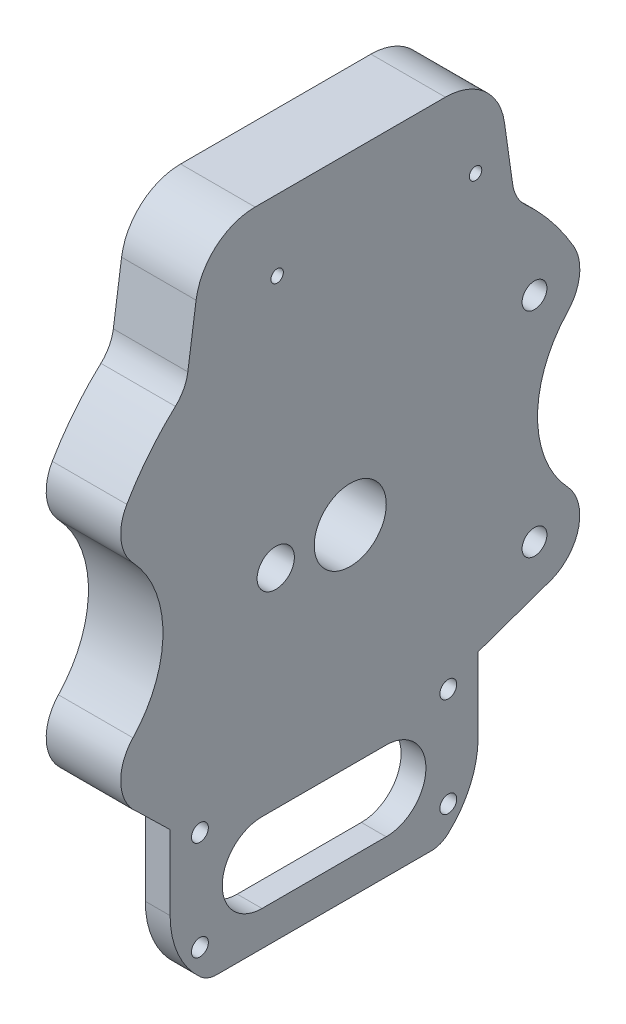
SolidWorks part; units mm, degrees
ref_plane "Płaszczyzna przednia" through (0, 0, 0) normal (0, 0, 1) x (1, 0, 0)
ref_plane "Płaszczyzna górna" through (0, 0, 0) normal (0, 1, 0) x (1, 0, 0)
ref_plane "Płaszczyzna prawa" through (0, 0, 0) normal (1, 0, 0) x (0, 0, -1)
sketch "Szkic1" plane through (0, 0, 0) normal (1, 0, 0) x (0, 0, -1)
  line L5 (0, 0) -> (0, 195.8303) construction
  line L42 (14.4695, -100) -> (-35.5305, -100) construction
  line L44 (14.4695, -84) -> (-35.5305, -84)
  line L45 (14.4695, -116) -> (-35.5305, -116)
  line L46 (30.5104, 100) -> (-9.4896, 100) construction
  line L47 (30.5104, 105) -> (-9.4896, 105) construction
  line L48 (30.5104, 95) -> (-9.4896, 95) construction
  line L49 (-10.5305, -100) -> (-10.5305, -46.7527) construction
  line L50 (-13.6636, -130) -> (20.5826, 195.8303) construction
  line L51 (0, 0) -> (120, 0) construction
  line L52 (0, 0) -> (0, -130.3815) construction
  line L53 (-72.5305, -70) -> (-85.8486, -57.0401)
  line L54 (-72.5305, -100) -> (-72.5305, -70)
  line L55 (51.4695, -70) -> (81.2407, -59.5241)
  line L56 (-35.5305, -130) -> (-53.6689, -130)
  line L57 (51.4695, -100) -> (51.4695, -70)
  line L58 (14.4695, -130) -> (32.6078, -130)
  line L59 (14.4695, -130) -> (-35.5305, -130)
  line L60 (62.0766, 109.386) -> (65.4007, 86.06)
  line L61 (-38.3166, 130) -> (38.3166, 130)
  line L62 (-62.0766, 109.386) -> (-65.4007, 86.06)
  circle A0 centre (0, 0) radius 14.5
  circle A3 centre (0, 0) radius 85.75 construction
  arc A56 (14.4695, -84) -> (14.4695, -116) centre (14.4695, -100) cw
  arc A57 (-35.5305, -116) -> (-35.5305, -84) centre (-35.5305, -100) cw
  arc A60 (30.5104, 105) -> (30.5104, 95) centre (30.5104, 100) cw construction
  arc A61 (-9.4896, 95) -> (-9.4896, 105) centre (-9.4896, 100) cw construction
  arc A62 (32.6078, -130) -> (39.3257, -127.4074) centre (32.6078, -120) ccw
  arc A63 (-60.3868, -127.4074) -> (-53.6689, -130) centre (-53.6689, -120) ccw
  arc A65 (51.4695, -100) -> (39.3257, -127.4074) centre (14.4695, -100) cw
  arc A66 (-60.3868, -127.4074) -> (-72.5305, -100) centre (-35.5305, -100) cw
  arc A67 (87.4958, -30.51) -> (81.2407, -59.5241) centre (74.4106, -42.8703) cw
  arc A68 (87.4958, -30.51) -> (87.4958, 30.51) centre (120, 0) cw
  arc A69 (89.9789, 52.1516) -> (87.4958, 30.51) centre (74.1894, 43) cw
  arc A70 (70.4086, 76.5417) -> (89.9789, 52.1516) centre (0, 0) cw
  arc A71 (65.4007, 86.06) -> (70.4086, 76.5417) centre (81.2407, 88.3174) ccw
  arc A72 (38.3166, 130) -> (62.0766, 109.386) centre (38.3166, 106) cw
  arc A73 (-38.3166, 130) -> (-62.0766, 109.386) centre (-38.3166, 106) ccw
  arc A74 (-65.4007, 86.06) -> (-70.4086, 76.5417) centre (-81.2407, 88.3174) cw
  arc A75 (-70.4086, 76.5417) -> (-89.9789, 52.1516) centre (0, 0) ccw
  arc A76 (-89.9789, 52.1516) -> (-87.4958, 30.51) centre (-74.1894, 43) ccw
  arc A77 (-87.4958, -30.51) -> (-87.4958, 30.51) centre (-120, 0) ccw
  arc A78 (-87.4958, -30.51) -> (-85.8486, -57.0401) centre (-74.1894, -43) ccw
  circle A79 centre (74.1894, -43) radius 5
  circle A80 centre (74.1894, 43) radius 5
  point P7 (-10.5305, -100)
  point P24 (-25, -70)
  point P25 (25, -70)
  point P30 (25, -100)
  point P31 (25, -130)
  point P33 (-25, -130)
  point P34 (-25, -100)
  point P41 (-25, -70)
  point P42 (25, -70)
  point P43 (-25.5104, 81)
  point P44 (25, -100)
  point P46 (-25, -130)
  point P47 (-25, -100)
  point P49 (62, -82.8995)
  point P58 (62, -100)
  point P59 (25, -100)
  point P60 (25, -137)
  point P61 (-25, -137)
  point P62 (-25, -100)
  point P63 (-62, -100)
  point P64 (-62, -82.8995)
  point P69 (10.5104, 100)
  point P72 (0, 126)
  point P192 (46.6564, -130)
  point P193 (-46.6564, -130)
  point P194 (74.1894, 43)
  point P195 (74.1894, -43)
  dimension "D1" = 29
  dimension "D7" = 171.5
extrude "Dodanie-wyciągnięcie1" add sketch "Szkic1" along normal mid plane 30
hole_wizard "Otwór gwintowany M61" positions "Sketch1" profile "Sketch2" tap size "M6" standard "ISO" end condition through all
sketch "Sketch1" plane through (-15, 0, 0) normal (1, 0, 0) x (0, 0, -1)
  line L0 (-81.5745, 104.2751) -> (63.3416, 96.6804) construction
  line L11 (0, 0) -> (0, 118.3984) construction
  line L12 (10.8009, 104.9924) -> (10.2776, 95.0061) construction
  point P50 (50.4556, 97.3557)
  point P51 (-29.4348, 101.5426)
  dimension "D1" = 93
  dimension "D2" = 40
  dimension "D3" = 40
sketch "Sketch2" plane through (-15, 101.5426, 29.4348) normal (0, 1, 0) x (0, 0, 1)
  line L0 (0, 0) -> (0, 30)
  line L1 (0, 30) -> (2.5, 30)
  line L2 (2.5, 30) -> (2.5, 0)
  line L5 (2.5, 0) -> (0, 0)
  line L11 (0, -6.35) -> (0, 107.95) construction
  dimension "Thru Tap Drill Dia." = 5
  dimension "Thru Tap Drill Depth" = 30
cosmetic thread "Gwint otworu5" parameters "D2"=6
cosmetic thread "Gwint otworu6" parameters "D2"=6
sketch "Szkic12" plane through (-15, 0, 0) normal (1, 0, 0) x (0, 0, -1)
  line L0 (0, 0) -> (0, 198.2502) construction
  line L1 (50.4556, 97.3557) -> (-29.4348, 101.5426) construction
  line L2 (28.8022, 93.4837) -> (-9.7329, 95.5032)
  line L3 (-9.2095, 105.4895) -> (29.3255, 103.47)
  arc A0 (-9.7329, 95.5032) -> (-9.2095, 105.4895) centre (-9.4712, 100.4964) cw
  arc A1 (29.3255, 103.47) -> (28.8022, 93.4837) centre (29.0639, 98.4768) cw
  circle A2 centre (-29.4348, 101.5426) radius 2.5 construction
  circle A3 centre (50.4556, 97.3557) radius 2.5 construction
  circle A4 centre (-29.4348, 101.5426) radius 2.5
  circle A5 centre (50.4556, 97.3557) radius 2.5
  point P0 (-30.2019, 101.5426)
  point P11 (0, 0)
  point P12 (0, 0)
  dimension "D3" = 5
  dimension "D1" = 93
  dimension "D2" = 10
extrude "Wytnij-wyciągnięcie2" cut sketch "Szkic12" along normal blind 10 contours A0 L3 A1 L2
sketch "Szkic16" plane through (-15, 0, 0) normal (1, 0, 0) x (0, 0, -1)
  line L5 (-35.5305, -116) -> (14.4695, -116)
  line L6 (14.4695, -84) -> (-35.5305, -84)
  line L8 (-53.6689, -130) -> (32.6078, -130)
  line L10 (-83.0611, -100) -> (40.9389, -100) construction
  line L11 (-72.5305, -70) -> (51.4695, -70)
  line L13 (-72.5305, -70) -> (-72.5305, -100)
  line L16 (51.4695, -70) -> (51.4695, -100)
  arc A6 (-35.5305, -84) -> (-35.5305, -116) centre (-35.5305, -100) ccw
  arc A7 (14.4695, -116) -> (14.4695, -84) centre (14.4695, -100) ccw
  arc A9 (32.6078, -130) -> (39.3257, -127.4074) centre (32.6078, -120) ccw
  arc A10 (-60.3868, -127.4074) -> (-53.6689, -130) centre (-53.6689, -120) ccw
  arc A20 (39.3257, -127.4074) -> (51.4695, -100) centre (14.4695, -100) ccw
  arc A21 (-72.5305, -100) -> (-60.3868, -127.4074) centre (-35.5305, -100) ccw
extrude "Wytnij-wyciągnięcie4" cut sketch "Szkic16" along normal blind 20
chamfer "Sfazowanie4" distance 10 angle 45 1 edges at (-15, -70, 10.5305)
sketch "Szkic17" plane through (-15, 0, 0) normal (1, 0, 0) x (0, 0, -1)
  line L2 (0, 0) -> (0, 36.4505) construction
  line L3 (-45.2929, 8.9572) -> (-31.5786, 10.9367)
  line L6 (-31.5786, -10.9367) -> (-45.2929, -8.9572)
  arc A7 (-45.2929, -8.9572) -> (-45.2929, 8.9572) centre (-44, 0) cw
  circle A8 centre (-30, 0) radius 7.5
  arc A10 (-18.9801, -0.8154) -> (-31.5786, -10.9367) centre (-30, 0) cw
  arc A12 (-31.5786, 10.9367) -> (-18.9801, -0.8154) centre (-30, 0) cw
  point P0 (8.9572, 38.7071)
  point P1 (-0.6678, 49.0253)
  point P2 (30, 0)
  point P3 (-8.9572, 38.7071)
  point P5 (-6.9777, 24.9929)
  point P6 (0, 26)
  point P7 (4.5988, 31.3435)
  point P8 (0, 26)
  point P9 (6.9777, 24.9929)
  point P20 (45.2929, -8.9572)
  point P21 (0, 26)
  point P22 (5.9035, 32.8594)
  point P23 (44, 0)
  point P24 (45.2929, 8.9572)
extrude "Wytnij-wyciągnięcie5" cut sketch "Szkic17" along normal blind 5 contours A8 | A7 L3 A12 A10 L6
extrude "Wytnij-wyciągnięcie6" cut sketch "Szkic17<5>" along normal through all contours A8
sketch "Szkic17<5>" plane through (-15, 0, 0) normal (1, 0, 0) x (0, 0, -1) same geometry as "Szkic17"
sketch "Szkic18" plane through (5, 0, 0) normal (-1, 0, 0) x (0, 0, 1)
  line L0 (10.5305, -84) -> (10.5305, -116) construction
  line L3 (-30.4695, -100) -> (51.5305, -100) construction
  point P14 (-39.4695, -77)
  point P17 (60.5305, -77)
  point P18 (60.5305, -117)
  point P19 (-39.4695, -117)
  dimension "D1" = 23
  dimension "D2" = 50
  dimension "D3" = 2
  dimension "D4" = 2
hole_wizard "Otwór gwintowany M81" positions "Szkic 3D1" profile "Szkic19" tap size "M8" standard "ISO"
sketch3d "Szkic 3D1"
  point P0 (5, -77, -39.4695)
  point P3 (5, -117, -39.4695)
  point P6 (5, -117, 60.5305)
  point P9 (5, -77, 60.5305)
sketch "Szkic19" plane through (5, -77, -39.4695) normal (0, 1, 0) x (0, 0, 1)
  line L0 (0, 0) -> (0, 18.25)
  line L1 (0, 18.25) -> (3.4, 16.2071)
  line L2 (3.4, 16.2071) -> (3.4, 0.625)
  line L3 (3.4, 0.625) -> (4.025, 0)
  line L5 (4.025, 0) -> (0, 0)
  line L6 (-3.4, 0.625) -> (-4.025, 0) construction
  line L10 (0, 18.25) -> (-3.4, 16.2071) construction
  line L11 (0, -6.35) -> (0, 107.95) construction
  dimension "Średnica wiertła gwintu" = 6.8
  dimension "Głębokość otworu gwintowanego" = 18.25
  dimension "Średnica zewnętrznego pogłębienia stożkowego" = 8.05
  dimension "Kąt zewnętrznego pogłębienia stożkowego" = 90
  dimension "Kąt wiertła" = 118
cosmetic thread "Gwint otworu1" parameters "D1"=10, "D2"=8
cosmetic thread "Gwint otworu2" parameters "D1"=10, "D2"=8
cosmetic thread "Gwint otworu3" parameters "D1"=10, "D2"=8
cosmetic thread "Gwint otworu4" parameters "D1"=10, "D2"=8
